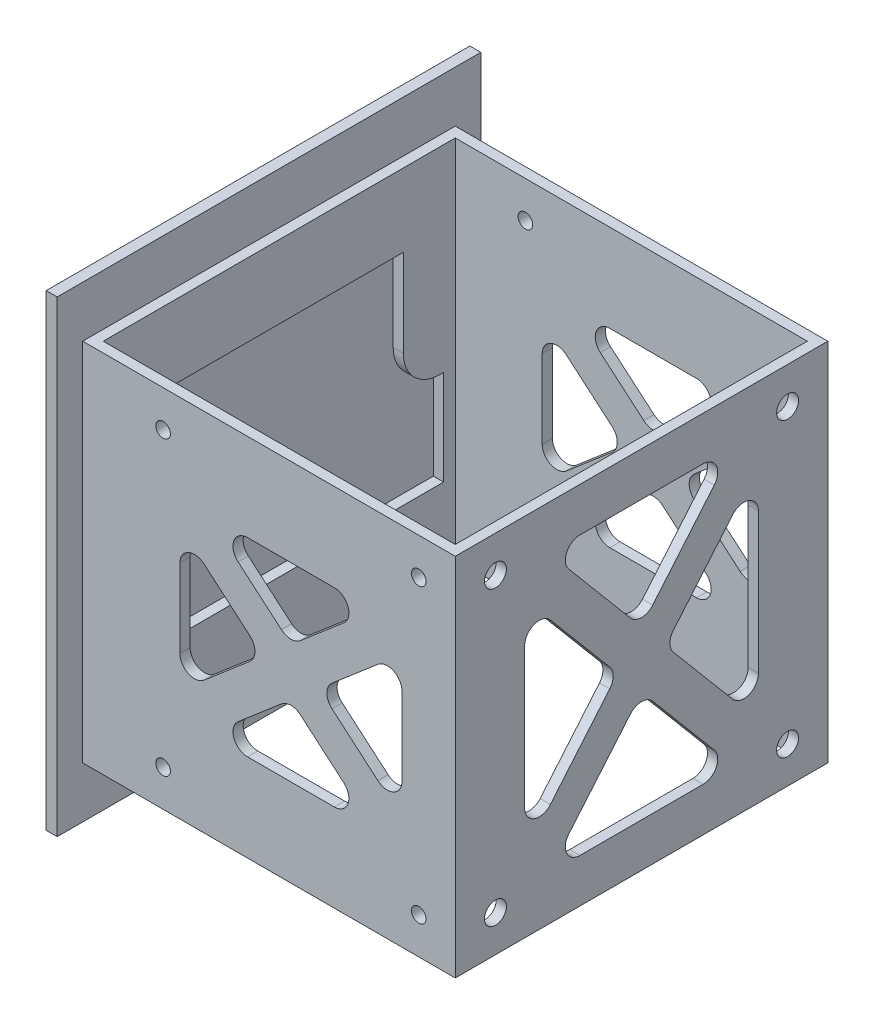
SolidWorks part; units mm, degrees
ref_plane "Plano frontal" through (0, 0, 0) normal (0, 0, 1) x (1, 0, 0)
ref_plane "Plano superior" through (0, 0, 0) normal (0, 1, 0) x (1, 0, 0)
ref_plane "Plano direito" through (0, 0, 0) normal (1, 0, 0) x (0, 0, -1)
sketch "Esboço1" plane through (0, 0, 0) normal (0, 1, 0) x (1, 0, 0)
  line L1 (25.5, 25.5) -> (-25.5, 25.5)
  line L2 (25.5, 25.5) -> (25.5, -25.5)
  line L3 (25.5, -25.5) -> (-25.5, -25.5)
  line L4 (-25.5, 25.5) -> (-25.5, -25.5)
  line L5 (25.5, 25.5) -> (-25.5, -25.5) construction
  line L6 (25.5, -25.5) -> (-25.5, 25.5) construction
  line L7 (24.1, 24.1) -> (-24.1, 24.1)
  line L8 (24.1, 24.1) -> (24.1, -24.1)
  line L9 (24.1, -24.1) -> (-24.1, -24.1)
  line L10 (-24.1, 24.1) -> (-24.1, -24.1)
  line L11 (24.1, 24.1) -> (-24.1, -24.1) construction
  line L12 (24.1, -24.1) -> (-24.1, 24.1) construction
  point P0 (0, 0)
  point P6 (0, 0)
  dimension "D1" = 51
  dimension "D2" = 51
  dimension "D3" = 1.4
  dimension "D4" = 1.4
extrude "Ressalto-extrusão1" add sketch "Esboço1" along normal blind 50
sketch "Esboço2" plane through (-25.5, 0, 0) normal (-1, 0, 0) x (0, 0, 1)
  line L0 (-25.5, 25) -> (25.5, 25) construction
  line L1 (29, 57) -> (-29, 57)
  line L2 (29, 57) -> (29, -7)
  line L3 (29, -7) -> (-29, -7)
  line L4 (-29, 57) -> (-29, -7)
  line L5 (29, 57) -> (-29, -7) construction
  line L6 (29, -7) -> (-29, 57) construction
  line L7 (-25.5, 50) -> (-25.5, 0) construction
  line L8 (25.5, 50) -> (25.5, 0) construction
  point P0 (0, 25)
  point P14 (0, 25)
  dimension "D1" = 64
  dimension "D2" = 58
extrude "Ressalto-extrusão2" add sketch "Esboço2" along normal blind 1.5 separate body
sketch "Esboço3" plane through (25.5, 0, 0) normal (1, 0, 0) x (0, 0, -1)
  line L0 (-25.5, 25) -> (25.5, 25) construction
  line L1 (20, 45) -> (-20, 45) construction
  line L2 (20, 45) -> (20, 5) construction
  line L3 (20, 5) -> (-20, 5) construction
  line L4 (-20, 45) -> (-20, 5) construction
  line L5 (20, 45) -> (-20, 5) construction
  line L6 (20, 5) -> (-20, 45) construction
  line L9 (14.0877, 45.6103) -> (-17.9123, 7.6103)
  line L10 (16, 44) -> (-16, 44)
  line L11 (16, 44) -> (16, 6)
  line L12 (16, 6) -> (-16, 6)
  line L13 (-16, 44) -> (-16, 6)
  line L14 (16, 44) -> (-16, 6) construction
  line L15 (16, 6) -> (-16, 44) construction
  line L16 (17.9123, 7.6103) -> (-14.0877, 45.6103)
  line L17 (17.9123, 42.3897) -> (-14.0877, 4.3897)
  line L18 (14.0877, 4.3897) -> (-17.9123, 42.3897)
  line L19 (25.5, 50) -> (25.5, 0) construction
  line L20 (-25.5, 50) -> (-25.5, 0) construction
  circle A0 centre (-20, 45) radius 1.5
  circle A1 centre (20, 45) radius 1.5
  circle A2 centre (20, 5) radius 1.5
  circle A3 centre (-20, 5) radius 1.5
  point P0 (0, 25)
  point P16 (0, 25)
  dimension "D3" = 3
  dimension "D1" = 40
  dimension "D2" = 40
  dimension "D4" = 38
  dimension "D5" = 32
  dimension "D6" = 2.5
  dimension "D7" = 2.5
extrude "Corte-extrusão1" cut sketch "Esboço3" against normal blind 1.5 contours L9 L18 L13 | L12 L18 L17 | L11 L17 L16 | L16 L9 L10 | A0 | A3 | A2 | A1 region at (25.5, 38.9604, 0) region at (25.5, 25, 11.7561) region at (25.5, 25, -11.7561) region at (25.5, 11.0396, 0) region at (25.5, 45, 20) region at (25.5, 45, -20) region at (25.5, 5, -20) region at (25.5, 5, 20)
fillet "Filete1" radius 2 12 edges at (24.8, 44, -12.7316) (24.8, 44, 12.7316) (24.8, 40.1188, 16) (24.8, 6, 12.7316) (24.8, 6, -12.7316) (24.8, 9.8812, -16) (24.8, 40.1188, -16) (24.8, 21.1188, 0) (24.8, 28.8812, 0) (24.8, 25, -3.2684) (24.8, 25, 3.2684) (24.8, 9.8812, 16)
sketch "Esboço4" plane through (0, 0, 25.5) normal (0, 0, 1) x (1, 0, 0)
  line L0 (25.5, 25) -> (-25.5, 25) construction
  line L1 (-14.5, 5) -> (20.5, 5) construction
  line L2 (-14.5, 5) -> (-14.5, 45) construction
  line L3 (-14.5, 45) -> (20.5, 45) construction
  line L4 (20.5, 5) -> (20.5, 45) construction
  line L5 (-14.5, 5) -> (20.5, 45) construction
  line L6 (-14.5, 45) -> (20.5, 5) construction
  line L7 (25.5, 50) -> (25.5, 0) construction
  line L8 (-25.5, -7) -> (-25.5, 57) construction
  line L9 (-25.5, 50) -> (25.5, 50) construction
  line L10 (18.2, 38) -> (-12.2, 38)
  line L11 (18.2, 38) -> (18.2, 12)
  line L12 (18.2, 12) -> (-12.2, 12)
  line L13 (-12.2, 38) -> (-12.2, 12)
  line L14 (18.2, 38) -> (-12.2, 12) construction
  line L15 (18.2, 12) -> (-12.2, 38) construction
  line L16 (16.5751, 39.8999) -> (-13.8249, 13.8999)
  line L17 (19.8249, 13.8999) -> (-10.5751, 39.8999)
  line L18 (19.8249, 36.1001) -> (-10.5751, 10.1001)
  line L19 (16.5751, 10.1001) -> (-13.8249, 36.1001)
  circle A0 centre (-14.5, 45) radius 1
  circle A1 centre (20.5, 45) radius 1
  circle A2 centre (20.5, 5) radius 1
  circle A3 centre (-14.5, 5) radius 1
  point P0 (3, 25)
  point P15 (3, 25)
  dimension "D4" = 2
  dimension "D1" = 35
  dimension "D2" = 40
  dimension "D3" = 5
  dimension "D5" = 12
  dimension "D6" = 7.3
  dimension "D7" = 2.5
  dimension "D8" = 2.5
extrude "Corte-extrusão2" cut sketch "Esboço4" against normal through all contours L16 L19 L13 | L12 L19 L18 | L11 L18 L17 | L17 L16 L10 | A0 | A3 | A2 | A1 region at (3, 34.7632, 25.5) region at (14.4154, 25, 25.5) region at (-8.4154, 25, 25.5) region at (3, 15.2368, 25.5) region at (-14.5, 45, 25.5) region at (20.5, 45, 25.5) region at (20.5, 5, 25.5) region at (-14.5, 5, 25.5)
fillet "Filete2" radius 2 24 edges at (18.2, 15.2896, 24.8) (18.2, 34.7104, 24.8) (14.3537, 38, 24.8) (-8.3537, 38, 24.8) (-12.2, 15.2896, 24.8) (-8.3537, 12, 24.8) (14.3537, 12, 24.8) (-0.8463, 25, 24.8) (6.8463, 25, 24.8) (3, 28.2896, 24.8) (14.3537, 12, -24.8) (18.2, 15.2896, -24.8) (-8.3537, 12, -24.8) (-12.2, 15.2896, -24.8) (18.2, 34.7104, -24.8) (14.3537, 38, -24.8) (-12.2, 34.7104, -24.8) (-8.3537, 38, -24.8) (3, 21.7104, -24.8) (6.8463, 25, -24.8) (-0.8463, 25, -24.8) (3, 28.2896, -24.8) (-12.2, 34.7104, 24.8) (3, 21.7104, 24.8)
sketch "Esboço5" plane through (25.5, 0, 0) normal (1, 0, 0) x (0, 0, -1)
  line L1 (-25.5, 0) -> (25.5, 0)
  line L2 (-25.5, 0) -> (-25.5, 50)
  line L3 (-25.5, 50) -> (25.5, 50)
  line L4 (25.5, 0) -> (25.5, 50)
extrude "Ressalto-extrusão3" [suppressed] add sketch "Esboço5" along normal blind 9 from offset 1
sketch "Esboço6" plane through (-24.1, 0, 0) normal (1, 0, 0) x (0, 0, -1)
  line L0 (-17, 40) -> (17, 40)
  line L1 (17, 40) -> (17, 28)
  line L2 (-17, 40) -> (-17, 28)
  line L3 (22, 23) -> (22.5, 23)
  line L4 (22.5, 23) -> (22.5, 10)
  line L5 (22.5, 10) -> (-22.5, 10)
  line L6 (-22.5, 10) -> (-22.5, 23)
  line L7 (-22.5, 23) -> (-22, 23)
  line L8 (24.1, 50) -> (-24.1, 50) construction
  line L9 (24.1, 0) -> (-24.1, 0) construction
  arc A0 (17, 28) -> (22, 23) centre (22, 28) ccw
  arc A1 (-17, 28) -> (-22, 23) centre (-22, 28) cw
  point P12 (0, 40)
  dimension "D6" = 5
  dimension "D1" = 10
  dimension "D2" = 34
  dimension "D3" = 45
  dimension "D4" = 10
  dimension "D5" = 27
extrude "Corte-extrusão3" cut sketch "Esboço6" against normal up to surface (1.4 mm away) up to face at (-25.5, 25, 0)
